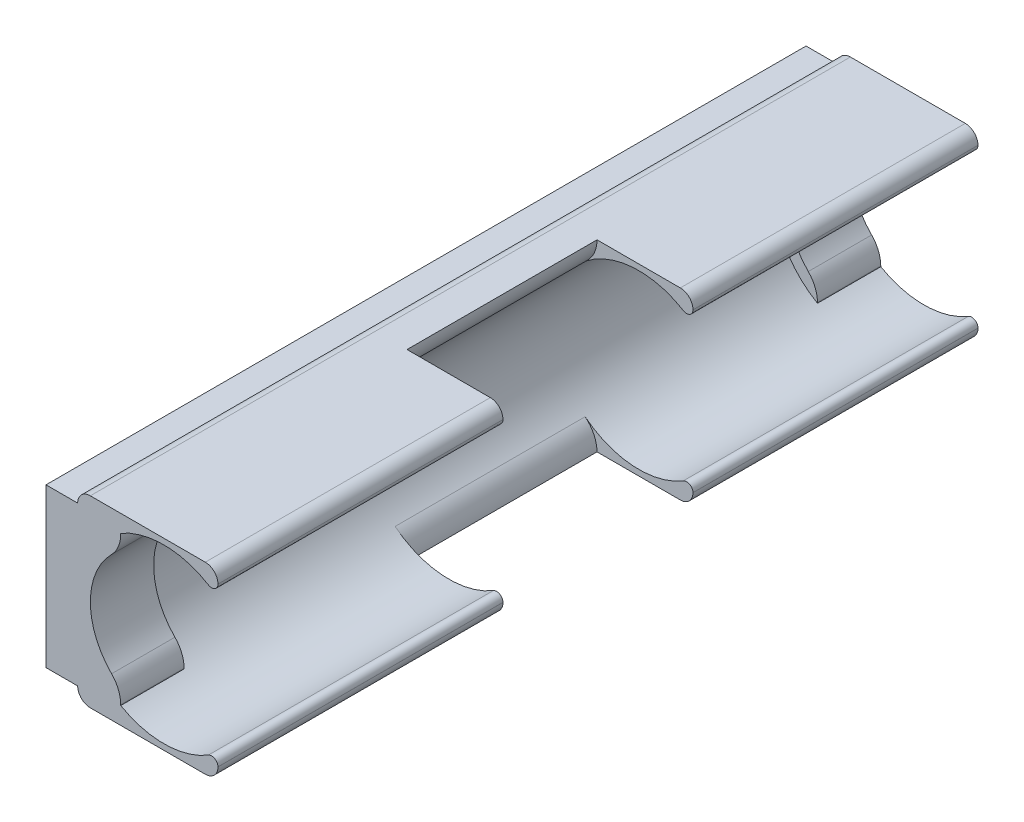
SolidWorks part; units mm, degrees
ref_plane "Front Plane" through (0, 0, 0) normal (0, 0, 1) x (1, 0, 0)
ref_plane "Top Plane" through (0, 0, 0) normal (0, 1, 0) x (1, 0, 0)
ref_plane "Right Plane" through (0, 0, 0) normal (1, 0, 0) x (0, 0, -1)
sketch "Sketch1" plane through (0, 0, 0) normal (1, 0, 0) x (0, 0, -1)
  line L1 (0, 0) -> (120, 0)
  line L2 (0, 0) -> (0, 25)
  line L3 (0, 25) -> (120, 25)
  line L4 (120, 0) -> (120, 25)
  dimension "D1" = 25
  dimension "D2" = 120
extrude "Base" add sketch "Sketch1" along normal blind 5
sketch "Sketch2" plane through (0, 0, 0) normal (0, 0, 1) x (1, 0, 0)
  line L0 (5, 25) -> (5, 0) construction
  line L1 (5, 25) -> (5, 0) construction
  line L2 (5, 12.5) -> (32.2, 12.5) construction
  line L5 (7, 27) -> (25.151, 27)
  line L6 (27.151, 23.0755) -> (27.151, 25)
  line L7 (7, -2) -> (25.151, -2)
  line L8 (27.151, 1.9245) -> (27.151, 0)
  line L9 (5, 0) -> (5, 25)
  circle A0 centre (18.6, 12.5) radius 13.6
  arc A1 (5, 25) -> (7, 27) centre (7, 25) cw
  arc A2 (25.151, 27) -> (27.151, 25) centre (25.151, 25) cw
  arc A3 (5, 0) -> (7, -2) centre (7, 0) ccw
  arc A4 (25.151, -2) -> (27.151, 0) centre (25.151, 0) ccw
  point P2 (5, 12.5)
  point P15 (7, 25)
  point P18 (27.151, 27)
  line M8 (5, 0) -> (5, 25)
  dimension "D1" = 27.2
  dimension "D4" = 2
  dimension "D5" = 2
  dimension "D2" = 20.25
  dimension "D3" = 2
extrude "Clip" add sketch "Sketch2" against normal up to surface (120 mm away) contours A2 L5 A1 A0 L6 M8 | L7 A4 L8 A0 A3 M8 region at (16.0755, 26.7353, 0) region at (12.6265, -0.0119, 0) up to face at (2.5, 12.5, -120)
sketch3d "3DSketch1"
  line L0 (0, 25, -120) -> (0, 25, 0) construction
  line L1 (0, 0, 0) -> (0, 0, -120) construction
  point P0 (0, 25, -60)
  point P1 (0, 0, -60)
ref_plane "Plane2" through (0, 0, -60) normal (0, 0, -1) x (-1, 0, 0)
sketch "Sketch3" plane through (0, 0, 0) normal (-1, 0, 0) x (0, 0, 1)
  line L0 (-120, 0) -> (-120, 25) construction
  line L1 (-60, 13.75) -> (-60, -13.75) construction
  circle A0 centre (-100, 12.5) radius 1.5
  circle A1 centre (-20, 12.5) radius 1.5
  point P4 (-120, 12.5)
  dimension "D1" = 3
  dimension "D2" = 20
extrude "ScrewHoles" cut sketch "Sketch3" against normal blind 3
sketch "Sketch4" plane through (0, 0, 0) normal (0, 0, 1) x (1, 0, 0)
  line L2 (18.6, 12.5) -> (5, 12.5)
  line L4 (11.8, 0.7221) -> (11.8, 0.8244)
  line L6 (11.8, 24.1756) -> (11.8, 24.2779)
  arc A1 (10.3542, 20.6589) -> (10.3542, 4.3411) centre (18.6, 12.5) ccw
  arc A2 (27.151, 23.0755) -> (27.151, 1.9245) centre (18.6, 12.5) ccw construction
  arc A3 (11.8, 24.2779) -> (11.8, 0.7221) centre (18.6, 12.5) ccw
  arc A4 (10.3542, 4.3411) -> (11.8, 0.8244) centre (6.8, 0.8244) cw
  arc A5 (10.3542, 20.6589) -> (11.8, 24.1756) centre (6.8, 24.1756) ccw
  point P5 (0, 0)
  point P11 (11.8, 12.5)
  point P12 (0, 0)
  point P13 (0, 0)
  point P14 (5.9674, 12.5)
  point P15 (5, 12.5)
  point P16 (0, 0)
  point P18 (18.6, 12.5)
  point P20 (11.8, 3.1021)
  point P23 (11.8, 21.8979)
  dimension "D1" = 2
  dimension "D2" = 5
extrude "ClipWall" add sketch "Sketch4" against normal blind 10 contours A1 A4 L4 A3 L6 A5
mirror "Mirror1" about plane through (0, 0, -60) normal (0, 0, -1) of "ClipWall"
fillet "RoundedCorners" radius 1 2 edges at (27.151, 1.9245, -60) (27.151, 23.0755, -60)
sketch "Sketch5" plane through (0, 0, -60) normal (0, 0, -1) x (-1, 0, 0)
  line L1 (-27.151, 27) -> (-12, 27)
  line L2 (-27.151, 27) -> (-27.151, -2)
  line L3 (-27.151, -2) -> (-12, -2)
  line L4 (-12, 27) -> (-12, -2)
  line L6 (-25.151, -2) -> (-7, -2) construction
  line L7 (-25.151, 27) -> (-7, 27) construction
  point P4 (0, 0)
  point P6 (0, 0)
  point P8 (-8.0688, 27.6776)
  point P9 (0, 0)
  point P13 (0, 0)
  point P16 (0, 0)
  dimension "D1" = 5
extrude "FingerGap" cut sketch "Sketch5" against normal mid plane 30
fillet "FingerGroove" radius 5 2 edges at (12, 0.6088, -60) (12, 24.3912, -60)
